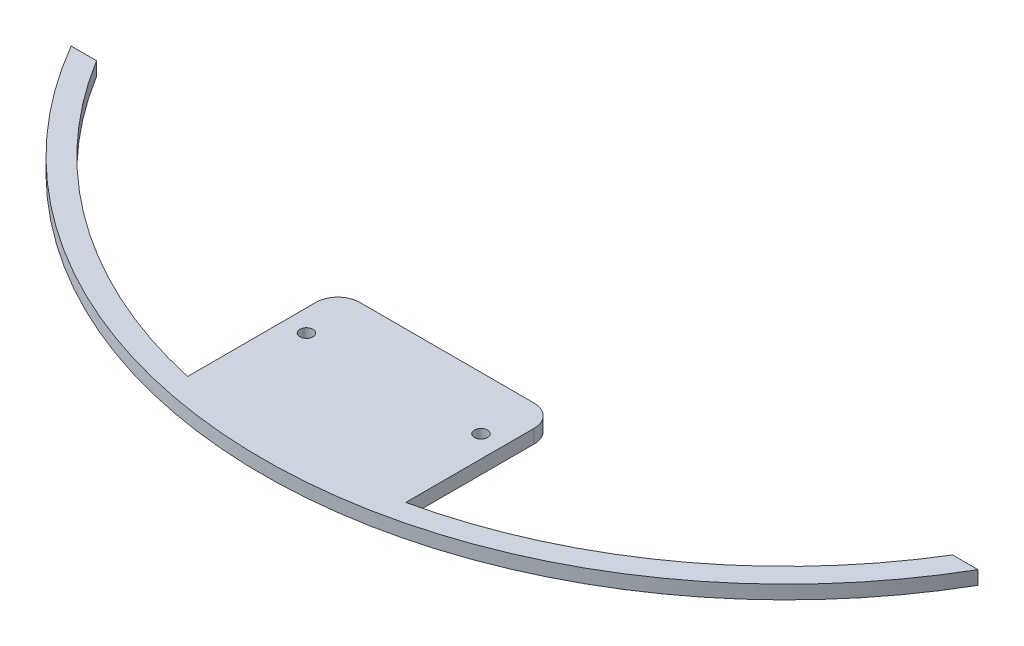
SolidWorks part; units mm, degrees
ref_plane "前视基准面" through (0, 0, 0) normal (0, 0, 1) x (1, 0, 0)
ref_plane "上视基准面" through (0, 0, 0) normal (0, 1, 0) x (1, 0, 0)
ref_plane "右视基准面" through (0, 0, 0) normal (1, 0, 0) x (0, 0, -1)
other "Configuration Table"
sketch "草图1" plane through (0, 0, 0) normal (0, 1, 0) x (1, 0, 0)
  line L0 (0, 0) -> (29.2916, 0) construction
  line L1 (0, 1410) -> (0, 205) construction
  line L2 (-103.923, 30) -> (-98.1071, 30)
  line L3 (-20, 12.1935) -> (20, 12.1935)
  line L4 (-25, 7.1935) -> (-25, -22.2497)
  line L6 (25, 7.1935) -> (25, -22.2497)
  line L7 (0, 30) -> (0, -27.5318) construction
  line L8 (98.1071, 30) -> (103.923, 30)
  arc A2 (20, 12.1935) -> (25, 7.1935) centre (20, 7.1935) cw
  arc A3 (-20, 12.1935) -> (-25, 7.1935) centre (-20, 7.1935) ccw
  arc A4 (-103.923, 30) -> (103.923, 30) centre (0, 90) ccw
  arc A5 (25, -22.2497) -> (98.1071, 30) centre (0, 90) ccw
  arc A6 (-98.1071, 30) -> (-25, -22.2497) centre (0, 90) ccw
  circle A7 centre (-20, 0) radius 1.5
  circle A8 centre (20, 0) radius 1.5
  point P9 (0, 12.1935)
  point P17 (25, 12.1935)
  point P20 (-25, 12.1935)
  point P21 (0, 90)
  dimension "D2" = 3
  dimension "D4" = 5
  dimension "D7" = 240
  dimension "D8" = 230
  dimension "D1" = 50
  dimension "D3" = 20
  dimension "D5" = 30
extrude "凸台-拉伸2" add sketch "草图1" along normal blind 3.125
